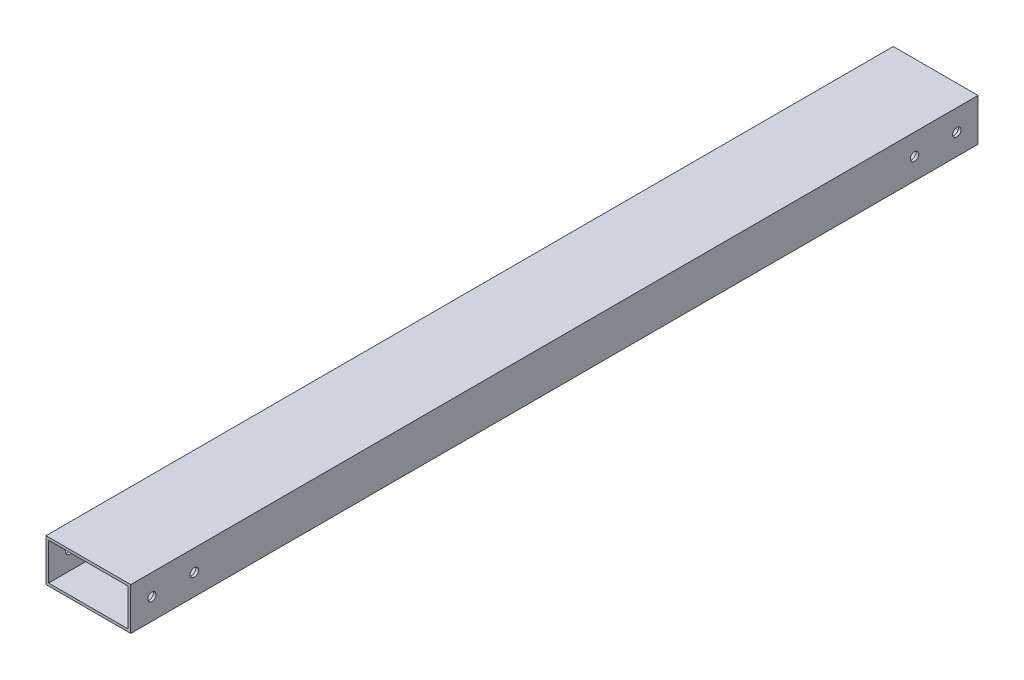
SolidWorks part; units mm, degrees
ref_plane "Front Plane" through (0, 0, 0) normal (0, 0, 1) x (1, 0, 0)
ref_plane "Top Plane" through (0, 0, 0) normal (0, 1, 0) x (1, 0, 0)
ref_plane "Right Plane" through (0, 0, 0) normal (1, 0, 0) x (0, 0, -1)
sketch "Sketch1" plane through (0, 0, 0) normal (0, 0, 1) x (1, 0, 0)
  line L0 (-23.8125, 11.1125) -> (23.8125, 11.1125)
  line L2 (-25.4, 12.7) -> (25.4, 12.7)
  line L3 (-25.4, 12.7) -> (-25.4, -12.7)
  line L4 (-25.4, -12.7) -> (25.4, -12.7)
  line L5 (25.4, 12.7) -> (25.4, -12.7)
  line L10 (23.8125, 11.1125) -> (23.8125, -11.1125)
  line L11 (-23.8125, -11.1125) -> (23.8125, -11.1125)
  line L12 (-23.8125, 11.1125) -> (-23.8125, -11.1125)
  point P12 (0, 12.7)
  point P14 (25.4, 0)
  dimension "Wall Thickness" = 1.5875
  dimension "Outside Width" = 50.8
  dimension "Outside Height" = 25.4
  dimension "Inside Height" = 22.225
  dimension "Inside Width" = 47.625
sketch "Sketch2" plane through (0, 0, 0) normal (1, 0, 0) x (0, 0, -1)
  line L0 (254, 0) -> (-254, 0)
  point P4 (0, 0)
  point P7 (-254, 0)
  point P10 (254, 0)
  dimension "Length" = 508
sketch "Sketch3" plane through (0, 0, 0) normal (0, 0, 1) x (1, 0, 0)
  line L21 (25.4, 12.7) -> (-25.4, 12.7)
  line L22 (25.4, -12.7) -> (25.4, 12.7)
  line L23 (-25.4, -12.7) -> (25.4, -12.7)
  line L24 (-25.4, 12.7) -> (-25.4, -12.7)
  line L25 (25.4, 12.7) -> (-25.4, 12.7)
  line L26 (25.4, -12.7) -> (25.4, 12.7)
  line L27 (-25.4, -12.7) -> (25.4, -12.7)
  line L28 (-25.4, 12.7) -> (-25.4, -12.7)
  line L29 (23.8125, 11.1125) -> (-23.8125, 11.1125)
  line L30 (23.8125, -11.1125) -> (23.8125, 11.1125)
  line L31 (-23.8125, -11.1125) -> (23.8125, -11.1125)
  line L32 (-23.8125, 11.1125) -> (-23.8125, -11.1125)
  line L33 (23.8125, 11.1125) -> (-23.8125, 11.1125)
  line L34 (23.8125, -11.1125) -> (23.8125, 11.1125)
  line L35 (-23.8125, -11.1125) -> (23.8125, -11.1125)
  line L36 (-23.8125, 11.1125) -> (-23.8125, -11.1125)
  dimension "D1" = 0
  dimension "D2" = 0
extrude "Boss-Extrude1" add sketch "Sketch3" along normal up to vertex (254 mm away) and the other way up to vertex (254 mm away) up to point (0, 0, 254) other way up to point (0, 0, -254)
sketch "Drawing Reference" plane through (0, 0, 0) normal (1, 0, 0) x (0, 0, -1)
  line L0 (-254, 0) -> (254, 0) construction
  line L1 (0, -12.7) -> (0, 12.7) construction
  line L2 (-254, -12.7) -> (254, -12.7) construction
  line L5 (-254, 12.7) -> (254, 12.7) construction
  point P7 (-217.424, 0)
  point P8 (217.424, 0)
  dimension "D1" = 36.576
hole_wizard "#10 Clearance Hole1" positions "Sketch4" profile "Sketch5" hole size "#10" standard "ANSI Inch" end condition through all
sketch "Sketch4" plane through (25.4, 0, 0) normal (1, 0, 0) x (0, 0, -1)
  point P0 (-241.3, 0)
  point P3 (-215.9, 0)
  point P6 (215.9, 0)
  point P9 (241.3, 0)
sketch "Sketch5" plane through (25.4, 0, 241.3) normal (0, 1, 0) x (0, 0, -1)
  line L0 (0, 0) -> (0, 50.8)
  line L1 (0, 50.8) -> (2.4892, 50.8)
  line L2 (2.4892, 50.8) -> (2.4892, 0)
  line L5 (2.4892, 0) -> (0, 0)
  line L11 (0, -6.35) -> (0, 107.95) construction
  dimension "Thru Hole Dia." = 4.9784
  dimension "Thru Hole Depth" = 50.8
equation "\"D1@Drawing Reference\"=\"Outside Width@Sketch1\" * 0.72"
